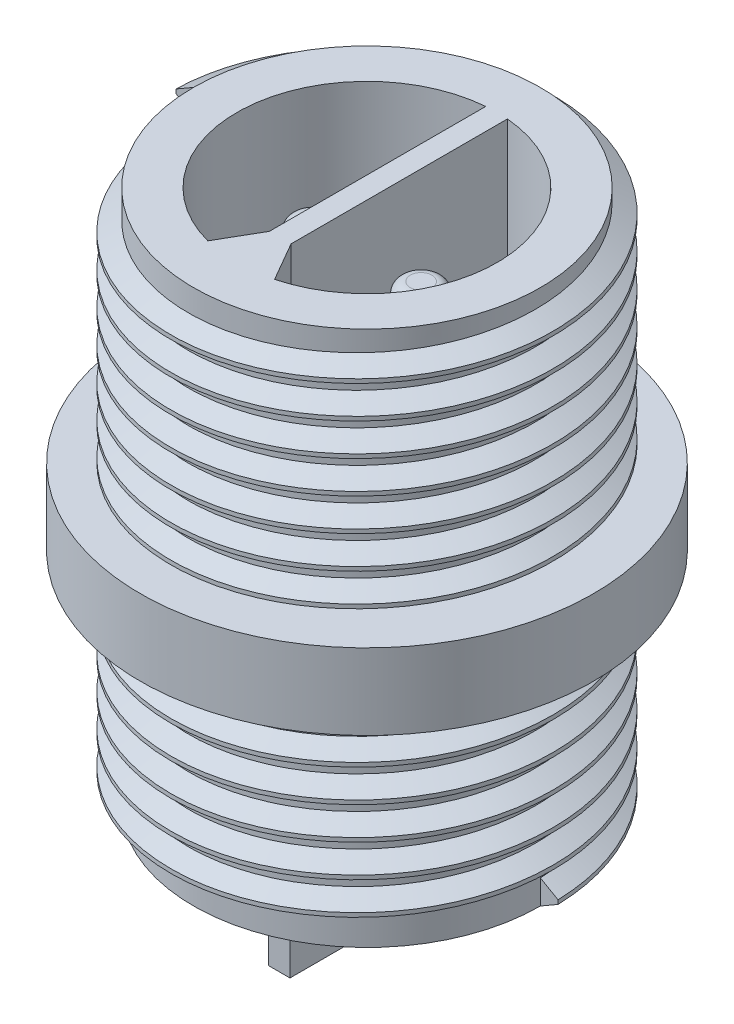
SolidWorks part; units mm, degrees
ref_plane "Front Plane" through (0, 0, 0) normal (0, 0, 1) x (1, 0, 0)
ref_plane "Top Plane" through (0, 0, 0) normal (0, 1, 0) x (1, 0, 0)
ref_plane "Right Plane" through (0, 0, 0) normal (1, 0, 0) x (0, 0, -1)
sketch "Sketch1" plane through (0, 0, 0) normal (0, 0, 1) x (1, 0, 0)
  line L0 (0, 0) -> (0, 20.0889) construction
  line L1 (0, 0) -> (8, 0)
  line L2 (8, 0) -> (8, 10.2)
  line L3 (8, 10.2) -> (10.45, 10.2)
  line L4 (10.45, 10.2) -> (10.45, 13.7)
  line L5 (10.45, 13.7) -> (8, 13.7)
  line L6 (8, 13.7) -> (8, 24.7)
  line L7 (8, 24.7) -> (0, 24.7)
  line L8 (0, 24.7) -> (0, 0)
  point P10 (9.225, 13.7)
  dimension "D1" = 8
  dimension "D2" = 10.45
  dimension "D3" = 11
  dimension "D4" = 10.2
  dimension "D5" = 3.5
revolve "Revolve1" add sketch "Sketch1" angle 360 about L0
sketch "Sketch2" plane through (0, 24.7, 0) normal (0, 1, 0) x (1, 0, 0)
  line L0 (0, 6) -> (0, -6) construction
  line L1 (-0.5, 6) -> (-0.5, -6)
  line L2 (0.5, 6) -> (0.5, -6)
  line L3 (-1.5388, -5.7993) -> (-0.5, -4)
  line L4 (-0.5, -4) -> (0.5, -4)
  line L5 (0.5, -4) -> (1.5388, -5.7993)
  circle A0 centre (0, 0) radius 6
  circle A1 centre (0, 0) radius 8 construction
  dimension "D1" = 2
  dimension "D4" = 30
  dimension "D5" = 30
  dimension "D6" = 2
  dimension "D2" = 0.5
  dimension "D3" = 0.5
extrude "Cut-Extrude1" cut sketch "Sketch2" against normal blind 7 contours L1 A0 L3 | L5 A0 L2 region at (-2.8603, 24.7, -0.1111) region at (2.8603, 24.7, -0.1111)
sketch "Sketch3" plane through (0, 0, 0) normal (0, -1, 0) x (1, 0, 0)
  line L1 (-0.5, -4.05) -> (0.5, -4.05)
  line L2 (-0.5, -4.05) -> (-0.5, 4.05)
  line L3 (-0.5, 4.05) -> (0.5, 4.05)
  line L4 (0.5, -4.05) -> (0.5, 4.05)
  line L5 (-0.5, -4.05) -> (0.5, 4.05) construction
  line L6 (-0.5, 4.05) -> (0.5, -4.05) construction
  point P0 (0, 0)
  dimension "D1" = 8.1
  dimension "D2" = 1
extrude "Boss-Extrude1" add sketch "Sketch3" along normal blind 4.6
sketch "Sketch4" plane through (0, 0, 0) normal (0, -1, 0) x (1, 0, 0)
  line L0 (-2.5, 0) -> (2.5, 0) construction
  circle A0 centre (-2.5, 0) radius 1
  circle A1 centre (2.5, 0) radius 1
  point P4 (0, 0)
  dimension "D1" = 2
  dimension "D2" = 2
  dimension "D3" = 5
extrude "Boss-Extrude2" add sketch "Sketch4" along normal blind 2.5 separate body
sketch "Sketch5" plane through (0, 17.7, 0) normal (0, 1, 0) x (1, 0, 0)
  circle A0 centre (2.5, 0) radius 1 construction
  circle A1 centre (-2.5, 0) radius 1 construction
  circle A2 centre (2.5, 0) radius 1
  circle A3 centre (-2.5, 0) radius 1
extrude "Boss-Extrude3" add sketch "Sketch5" along normal blind 4.5 separate body
fillet "Fillet2" radius 0.5 1 edges at (-2.5, 22.2, 1)
fillet "Fillet3" radius 0.5 1 edges at (2.5, 22.2, 1)
thread "Thread1" pitch 1.5 method extrude profile "Thread Profile2" start angle 0, offset 0, length 0, pitch 1.5, diameter 16
ref_plane "Plane2" through (-8, 24.7, 0) normal (0, 0, 1) x (-1, 0, 0)
sketch "Thread Profile2" plane through (-8, 24.7, 0) normal (0, 0, 1) x (-1, 0, 0)
  line L0 (0, 0) -> (0, 1.5) construction
  line L1 (0, 0) -> (0.8119, 0.4687)
  line L2 (0.8119, 0.4687) -> (0.8119, 0.6562)
  line L3 (0.8119, 0.6562) -> (0, 1.125)
  line L4 (0.8119, 0.5625) -> (0, 0.5625) construction
  line L11 (0, 0) -> (0, 1.125)
  point P2 (0, 0)
  dimension "Pitch" = 1.5
  dimension "Profile_Angle" = 60
  dimension "Profile_Land" = 0.1875
  dimension "Profile_Height" = 0.8119
thread "Thread2" pitch 1.5 method extrude profile "Thread Profile3" start angle 0, offset 0, length 0, pitch 1.5, diameter 16
ref_plane "Plane3" through (8, 0, 0) normal (0, 0, 1) x (1, 0, 0)
sketch "Thread Profile3" plane through (8, 0, 0) normal (0, 0, 1) x (1, 0, 0)
  line L0 (0, 0) -> (0, 1.5) construction
  line L1 (0, 0) -> (0.8119, 0.4687)
  line L2 (0.8119, 0.4687) -> (0.8119, 0.6562)
  line L3 (0.8119, 0.6562) -> (0, 1.125)
  line L4 (0.8119, 0.5625) -> (0, 0.5625) construction
  line L11 (0, 0) -> (0, 1.125)
  point P2 (0, 0)
  dimension "Pitch" = 1.5
  dimension "Profile_Angle" = 60
  dimension "Profile_Land" = 0.1875
  dimension "Profile_Height" = 0.8119
